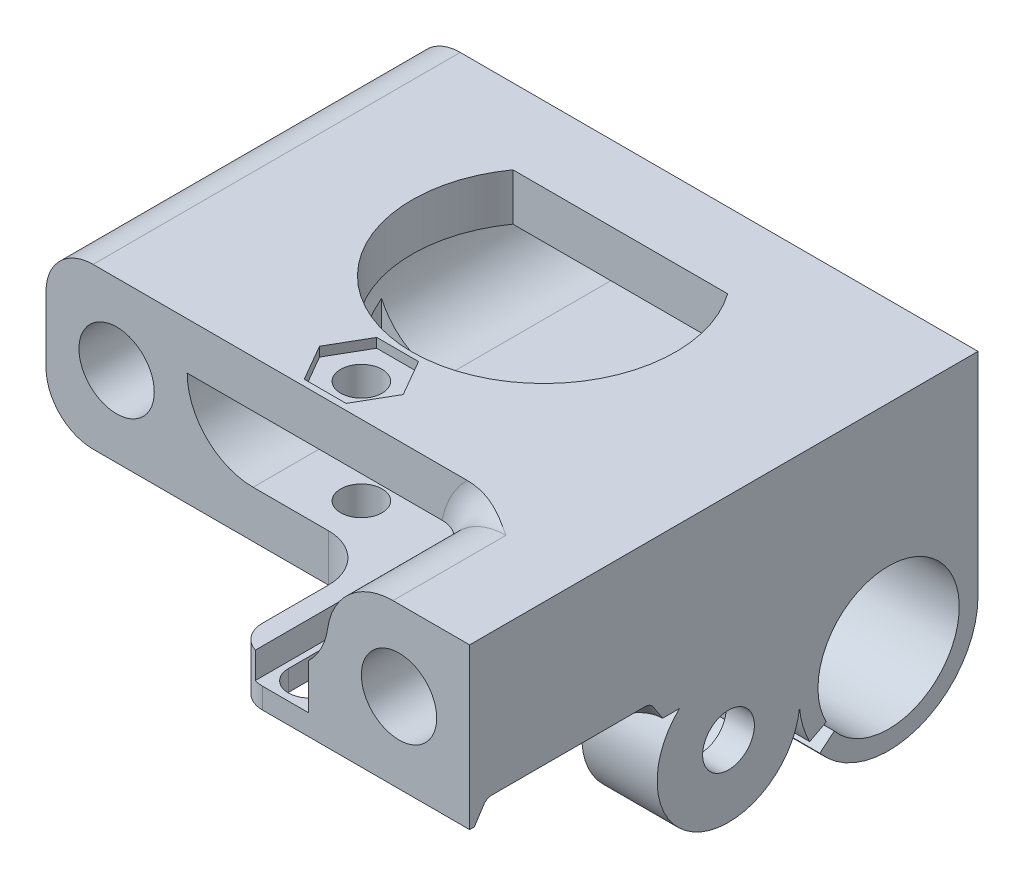
SolidWorks part; units mm, degrees
material "ABS generico"
ref_plane "Front Plane" through (0, 0, 0) normal (0, 0, 1) x (1, 0, 0)
ref_plane "Top Plane" through (0, 0, 0) normal (0, 1, 0) x (1, 0, 0)
ref_plane "Right Plane" through (0, 0, 0) normal (1, 0, 0) x (0, 0, -1)
sketch "Sketch1" plane through (0, 0, 0) normal (1, 0, 0) x (0, 0, -1)
  line L1 (21.1236, -26.9641) -> (22.8813, -26.0274)
  line L3 (23.7305, -27.2923) -> (22.1984, -28.5649)
  line L4 (20.0416, -23.294) -> (20.0416, -17)
  line L8 (39, 0) -> (0, 0)
  line L12 (0, -17) -> (0, 0)
  line L13 (0, -17) -> (20.0416, -17)
  line L15 (39, -22.5) -> (39, 0)
  line L19 (16.5, -29.4282) -> (20.0416, -23.294) construction
  line L20 (8.5, -29.4282) -> (16.5, -29.4282) construction
  line L21 (4.5, -22.5) -> (8.5, -29.4282) construction
  line L22 (4.5, -17) -> (4.5, -22.5) construction
  arc A0 (23.7305, -27.2923) -> (22.8813, -26.0274) centre (29.5041, -22.4988) ccw
  arc A1 (20.0416, -23.294) -> (21.1236, -26.9641) centre (29.5041, -22.4988) ccw
  arc A2 (22.1984, -28.5649) -> (39, -22.5) centre (29.5041, -22.4988) ccw
  circle A5 centre (12.5, -22.5) radius 2.75 construction
  dimension "D2" = 7.5042
  dimension "D3" = 9.4959
  dimension "D1" = 39
  dimension "D4" = 17
extrude "Extrude1" add sketch "Sketch1" against normal blind 60
sketch "Sketch2" plane through (0, 0, 0) normal (0, 0, 1) x (1, 0, 0)
  line L0 (-60, -8.5) -> (0, -8.5) construction
  line L1 (-60, 0) -> (-60, -17) construction
  line L2 (0, 0) -> (0, -17) construction
  line L3 (-30, 1.8171) -> (-30, -40.9837) construction
  line L5 (-15, -12) -> (-45, -12)
  line L6 (-15, -12) -> (-15, -5)
  line L7 (-15, -5) -> (-45, -5)
  line L8 (-45, -12) -> (-45, -5)
  line L9 (-15, -12) -> (-45, -5) construction
  line L10 (-15, -5) -> (-45, -12) construction
  circle A0 centre (-52.5, -8.5) radius 4
  circle A1 centre (-7.5, -8.5) radius 4
  point P12 (-30, -8.5)
  dimension "D1" = 8
  dimension "D2" = 22.5
  dimension "D3" = 7.5
  dimension "D4" = 7
  dimension "D5" = 30
extrude "Extrude2" cut sketch "Sketch2" against normal up to surface (39 mm away) up to face at (-30, -11.25, -39)
sketch "Sketch3" plane through (0, 0, 0) normal (0, 0, 1) x (1, 0, 0)
  line L0 (-52.5, -8.5) -> (-7.5, -8.5) construction
  line L1 (-52.5, -8.5) -> (-52.5, 8.8734) construction
  line L2 (-32.5, -8.5) -> (-32.5, 8.8734) construction
  dimension "D1" = 20
sketch "Sketch4" plane through (0, 0, 0) normal (1, 0, 0) x (0, 0, -1)
  line L0 (7.2804, -17) -> (20.0416, -17)
  line L1 (12.5, -17.9967) -> (8.6, -20.2483) construction
  line L2 (8.6, -20.2483) -> (8.6, -24.7517) construction
  line L3 (8.6, -24.7517) -> (12.5, -27.0033) construction
  line L4 (12.5, -27.0033) -> (16.4, -24.7517) construction
  line L5 (16.4, -24.7517) -> (16.4, -20.2483) construction
  line L6 (16.4, -20.2483) -> (12.5, -17.9967) construction
  line L7 (0, -17) -> (20.0416, -17) construction
  line L8 (20.0416, -17) -> (20.0817, -22.3872)
  circle A0 centre (12.5, -22.5) radius 3.9 construction
  arc A1 (7.2804, -17) -> (20.0817, -22.3872) centre (12.5, -22.5) ccw
  dimension "D1" = 7.8
extrude "Extrude3" add sketch "Sketch4" against normal blind 8
sketch "Sketch5" plane through (0, 0, 0) normal (1, 0, 0) x (0, 0, -1)
  circle A0 centre (12.5, -22.5) radius 2.75
  dimension "D1" = 5.5
extrude "Extrude4" cut sketch "Sketch5" against normal up to surface (8 mm away) up to face at (-8, -22.1484, -14.2839)
sketch "Sketch6" plane through (-8, 0, 0) normal (-1, 0, 0) x (0, 0, 1)
  line L1 (-12.5, -17.8812) -> (-16.5, -20.1906)
  line L2 (-16.5, -20.1906) -> (-16.5, -24.8094)
  line L3 (-16.5, -24.8094) -> (-12.5, -27.1188)
  line L4 (-12.5, -27.1188) -> (-8.5, -24.8094)
  line L5 (-8.5, -24.8094) -> (-8.5, -20.1906)
  line L6 (-8.5, -20.1906) -> (-12.5, -17.8812)
extrude "Extrude5" cut sketch "Sketch6" against normal blind 5
sketch "Sketch7" plane through (0, 0, 0) normal (0, 1, 0) x (1, 0, 0)
  line L2 (-31, -370.8295) -> (-31, 97.9462) construction
  line L6 (-30.9897, -180.6724) -> (-30.9897, -405.4164) construction
  circle A0 centre (-31, 4.5) radius 2.2
extrude "Extrude6" cut sketch "Sketch7" against normal up to surface (17 mm away) up to face at (-22.6667, -17, -9.1073)
sketch "Sketch8" plane through (0, 0, -39) normal (0, 0, -1) x (-1, 0, 0)
  line L0 (7.5, -8.5) -> (52.5, -8.5) construction
  line L1 (30, -8.5) -> (30, 3.0319) construction
  circle A0 centre (7.5, -8.5) radius 4.201
  circle A1 centre (52.5, -8.5) radius 1.25
  circle A2 centre (7.5, -8.5) radius 1.25
  circle A3 centre (52.5, -8.5) radius 4.201
  dimension "D1" = 2.5
extrude "Extrude7" add sketch "Sketch8" against normal blind 5
sketch "Sketch10" plane through (-60, 0, 0) normal (-1, 0, 0) x (0, 0, 1)
  line L1 (-20.0416, -17) -> (-39.247, -17)
  line L2 (-20.0416, -17) -> (-20.0416, -32.1139)
  line L3 (-20.0416, -32.1139) -> (-39.247, -32.1139)
  line L4 (-39.247, -17) -> (-39.247, -32.1139)
extrude "Extrude8" cut sketch "Sketch10" against normal blind 10
fillet "Fillet9" radius 10 2 edges at (-55, -17, -24.3976) (-55, -17, -34.6107)
fillet "Fillet11" radius 5 1 edges at (-60, 0, -19.5)
fillet "Fillet12" radius 5 5 edges at (-60, -17, -38.3198) (-60, -16.7094, -35.2462) (-60, -14.9946, -29.5041) (-60, -16.7094, -23.7621) (-60, -17, -10.6843)
sketch "Sketch12" plane through (0, 0, 0) normal (0, 0, 1) x (1, 0, 0)
  line L0 (-15, -12) -> (-15, 2.5343) construction
  line L1 (0, 0) -> (-20.7492, 0) construction
  line L2 (-55, 0) -> (0, 0) construction
  line L3 (-45, -12) -> (-15, -12) construction
  line L4 (-15, 0) -> (0, 0)
  line L5 (-11.5, -8.5) -> (-11.5, 2.5343) construction
  line L6 (-15, -17) -> (0, -17)
  line L7 (0, 0) -> (0, -17)
  line L8 (-15, -17) -> (-25, -17)
  line L9 (-25, -12) -> (-15, -12)
  line L10 (-15, -12) -> (-15, 0)
  line L11 (-25, -17) -> (-25, -12)
  circle A0 centre (-7.5, -8.5) radius 4
  point P21 (-14.5, -8.5)
  point P22 (-14.5, 2.5343)
  dimension "D3" = 8
  dimension "D1" = 10
extrude "Extrude10" add sketch "Sketch12" along normal blind 15
sketch "Sketch13" plane through (0, -17, 0) normal (0, -1, 0) x (1, 0, 0)
  line L2 (-20, -5.2455) -> (-20, 23.7024) construction
  line L4 (-25, 0) -> (-9.3359, 0) construction
  line L5 (-25, 15) -> (-25, 0) construction
  line L6 (-20, 12) -> (-20, -3) construction
  line L7 (-17.75, 12) -> (-17.75, -3)
  line L8 (-22.25, 12) -> (-22.25, -3)
  line L9 (-25, 15) -> (0, 15) construction
  arc A0 (-17.75, 12) -> (-22.25, 12) centre (-20, 12) ccw
  arc A1 (-22.25, -3) -> (-17.75, -3) centre (-20, -3) ccw
  point P14 (-20, 4.5)
  dimension "D2" = 3
  dimension "D1" = 5
extrude "Extrude11" cut sketch "Sketch13" against normal up to surface (5 mm away) up to face at (-28.8, -12, -4.5)
sketch "Sketch14" plane through (0, -17, 0) normal (0, -1, 0) x (1, 0, 0)
  line L0 (1.5, -3) -> (1.5, 12)
  line L1 (-12, -10.2024) -> (-12, 22.3262) construction
  line L2 (-1.5, 12) -> (-1.5, -3)
  line L3 (-10.5, -3) -> (-10.5, 12)
  line L4 (-13.5, 12) -> (-13.5, -3)
  arc A0 (-1.5, -3) -> (1.5, -3) centre (0, -3) ccw
  arc A1 (1.5, 12) -> (-1.5, 12) centre (0, 12) ccw
  arc A2 (-10.5, 12) -> (-13.5, 12) centre (-12, 12) ccw
  arc A3 (-13.5, -3) -> (-10.5, -3) centre (-12, -3) ccw
extrude "Extrude12" cut sketch "Sketch14" against normal blind 2
chamfer "Chamfer1" distance 1 angle 45 4 edges at (-13.5, -17, 4.5) (-12, -17, -4.5) (-12, -17, 13.5) (-10.5, -17, 4.5)
fillet "Fillet15" radius 3 1 edges at (-25, -14.5, 15)
sketch "Sketch15" plane through (0, 0, 0) normal (0, 1, 0) x (1, 0, 0)
  line L0 (-50, 22.8813) -> (0, 22.8813) construction
  line L1 (-41.4058, 31) -> (-18.5942, 31)
  arc A0 (-41.4058, 31) -> (-18.5942, 31) centre (-30, 22.8813) ccw
extrude "Extrude13" cut sketch "Sketch15" against normal blind 9
fillet "Fillet18" radius 1 4 edges at (-13.5, -15, 4.5) (-12, -15, 13.5) (-10.5, -15, 4.5) (-12, -15, -4.5)
fillet "Fillet19" radius 11 4 edges at (-13.5, -16, 4.5) (-12, -16, 13.5) (-10.5, -16, 4.5) (-12, -16, -4.5)
fillet "Fillet20" radius 7 1 edges at (-45, -12, -19.5)
sketch "Sketch16" plane through (0, -17, 0) normal (0, -1, 0) x (1, 0, 0)
  line L0 (-30, -8.881) -> (-30, -22.8813) construction
  line L1 (-44.4017, -20.0416) -> (-15.5983, -20.0416)
  arc A1 (-15.5983, -20.0416) -> (-44.4017, -20.0416) centre (-30, -22.8813) ccw
extrude "Extrude14" cut sketch "Sketch16" against normal up to surface (12 mm away) up to face at (-30, -5, -19.9405)
fillet "Fillet21" radius 7 1 edges at (-15, -12, -12)
fillet "Fillet22" radius 5 1 edges
sketch "Sketch17" plane through (0, 0, 0) normal (0, 1, 0) x (1, 0, 0)
  line L7 (-35.4444, 4.5) -> (-33.2222, 0.651)
  line L8 (-33.2222, 0.651) -> (-28.7778, 0.651)
  line L9 (-28.7778, 0.651) -> (-26.5556, 4.5)
  line L10 (-26.5556, 4.5) -> (-28.7778, 8.349)
  line L11 (-28.7778, 8.349) -> (-33.2222, 8.349)
  line L12 (-33.2222, 8.349) -> (-35.4444, 4.5)
  circle A0 centre (-31, 4.5) radius 3.849 construction
extrude "Cut-Extrude1" cut sketch "Sketch17" against normal blind 1
sketch "Sketch18" plane through (0, -5, 0) normal (0, -1, 0) x (1, 0, 0)
  line L0 (-20, -5.25) -> (-20, 17.0853) construction
  line L1 (-17.1, -3) -> (-17.1, 17.0853)
  line L2 (-22.9, -3) -> (-22.9, 17.0853)
  line L3 (-16.6454, -3) -> (-23.5438, -3) construction
  line L4 (-22.9, 17.0853) -> (-17.1, 17.0853)
  line L5 (-22.9, -5.25) -> (-22.9, 17.0853) construction
  line L6 (-17.1, -5.25) -> (-17.1, 17.0853) construction
  arc A0 (-22.25, -3) -> (-17.75, -3) centre (-20, -3) ccw construction
  arc A1 (-22.9, -3) -> (-17.1, -3) centre (-20, -3.7681) ccw
  dimension "D1" = 2.9
  dimension "D2" = 2.9
extrude "Cut-Extrude2" cut sketch "Sketch18" along normal blind 9.8
fillet "Fillet33" radius 7 1 edges
fillet "Fillet34" radius 3 1 edges at (-12.3269, -1.3875, 0)
chamfer "Chamfer4" distance 1 angle 57 3 edges at (-1.0607, -17, 13.0607) (-1.0607, -17, -4.0607) (-1.5, -17, 4.5) first distance on face at (-22.4282, -17, -3.1966)
fillet "Fillet39" radius 1 3 edges at (-1.0607, -15, 13.0607) (-1.0607, -15, -4.0607) (-1.5, -15, 4.5)
